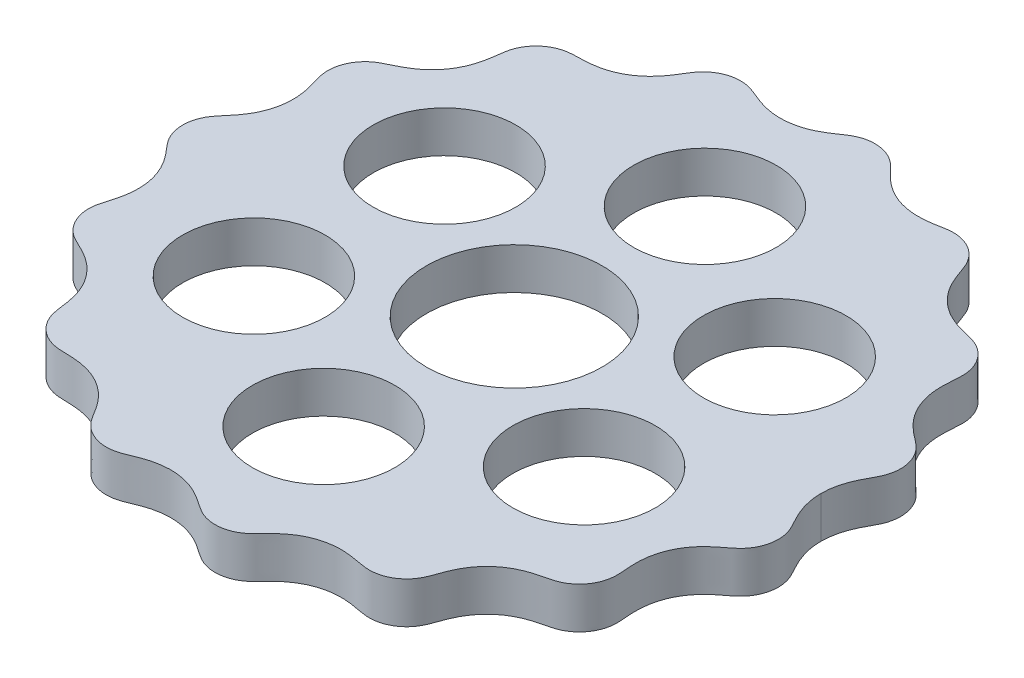
SolidWorks part; units mm, degrees
ref_plane "Front Plane" through (0, 0, 0) normal (0, 0, 1) x (1, 0, 0)
ref_plane "Top Plane" through (0, 0, 0) normal (0, 1, 0) x (1, 0, 0)
ref_plane "Right Plane" through (0, 0, 0) normal (1, 0, 0) x (0, 0, -1)
sketch "Sketch1" plane through (0, 0, 0) normal (0, 1, 0) x (1, 0, 0)
  circle A0 centre (0, 0) radius 10.6
  circle A1 centre (0, 0) radius 23 construction
  circle A2 centre (0, 23) radius 8.6
  circle A3 centre (19.9186, 11.5) radius 8.6
  circle A4 centre (19.9186, -11.5) radius 8.6
  circle A5 centre (0, -23) radius 8.6
  circle A6 centre (-19.9186, -11.5) radius 8.6
  circle A7 centre (-19.9186, 11.5) radius 8.6
  spline S0 degree 4 poles (38.6756, 9.5405) (38.7869, 9.3354) (38.9807, 8.9098) (39.18, 8.2438) (39.2638, 7.3275) (39.17, 6.4698) (38.9321, 5.7015) (38.5995, 5.0253) (38.2553, 4.4109) (37.9563, 3.8443) (37.7129, 3.322) (37.522, 2.8468) (37.3939, 2.4766) (37.2981, 2.1548) (37.2278, 1.884) (37.1776, 1.6659) (37.1334, 1.4465) (37.0953, 1.226) (37.0635, 1.0045) (37.0411, 0.8091) (37.0259, 0.6435) (37.0159, 0.5055) (37.0095, 0.392) (37.0035, 0.2438) (36.9999, 0.079) (36.9994, -0.0361) (37.0025, -0.21) (37.0079, -0.366) (37.0181, -0.5474) (37.0358, -0.7626) (37.0623, -1.0007) (37.0996, -1.2541) (37.1417, -1.4901) (37.1867, -1.7077) (37.276, -2.0862) (37.4326, -2.6197) (37.6503, -3.1917) (37.9334, -3.7956) (38.206, -4.3157) (38.4505, -4.7606) (38.7069, -5.2352) (38.9418, -5.7567) (39.1379, -6.3788) (39.248, -7.1039) (39.2286, -7.94) (39.0193, -8.8558) (38.5776, -9.8235) (37.821, -10.7544) (36.8481, -11.435) (35.9255, -12.1707) (35.1552, -12.9314) (34.5438, -13.6951) (33.8952, -14.742) (33.4284, -15.8904) (33.1613, -17.1041) (33.0908, -18.2767) (33.1179, -19.1348) (33.1846, -19.9227) (33.2426, -20.6446) (33.2196, -21.4379) (33.0363, -22.2817) (32.6622, -23.1285) (32.0787, -23.9264) (31.2705, -24.6475) (30.2129, -25.1958) (29.0562, -25.4259) (27.9212, -25.7148) (26.9129, -26.088) (26.0467, -26.5265) (25.2315, -27.0702) (24.4863, -27.7162) (23.8232, -28.4568) (23.2548, -29.2804) (22.819, -30.1054) (22.4892, -30.9045) (22.2262, -31.656) (21.9863, -32.3444) (21.6457, -33.0672) (21.1369, -33.7721) (20.4446, -34.4052) (19.5735, -34.9081) (18.6791, -35.1912) (17.8142, -35.2793) (17.018, -35.2129) (16.3018, -35.0765) (15.5195, -34.9284) (14.6625, -34.8147) (13.4804, -34.7697) (12.2411, -34.9196) (11.052, -35.2755) (9.9494, -35.8202) (9.1364, -36.3513) (8.3091, -37.0378) (7.4914, -37.8764) (6.7137, -38.763) (5.7101, -39.4048) (4.6815, -39.7442) (3.6987, -39.8506) (2.7784, -39.7512) (1.9559, -39.488) (1.2575, -39.1113) (0.6613, -38.7001) (0.0122, -38.2484) (-0.7173, -37.7958) (-1.768, -37.2706) (-2.9527, -36.8951) (-4.1807, -36.7251) (-5.4116, -36.7634) (-6.3787, -36.9109) (-7.4226, -37.1978) (-8.5211, -37.6287) (-9.5969, -38.1313) (-10.7814, -38.3206) (-11.8653, -38.2177) (-12.81, -37.9179) (-13.7654, -37.3701) (-14.6397, -36.51) (-15.225, -35.4471) (-15.8752, -34.4321) (-16.7227, -33.382) (-17.6452, -32.5494) (-18.6953, -31.8812) (-19.8393, -31.4031) (-20.7931, -31.1347) (-21.8817, -30.9645) (-23.0854, -30.9087) (-24.2988, -30.9334) (-25.4807, -30.6062) (-26.4329, -30.0527) (-27.1648, -29.3844) (-27.7959, -28.4973) (-28.2242, -27.3768) (-28.3269, -26.1938) (-28.503, -25.027) (-28.7764, -23.9796) (-29.1322, -23.0683) (-29.7145, -21.9831) (-30.4757, -21.0047) (-31.3933, -20.1664) (-32.3735, -19.5191) (-33.1302, -19.1136) (-33.8459, -18.7774) (-34.5001, -18.4667) (-35.1756, -18.0501) (-35.8147, -17.4694) (-36.361, -16.7221) (-36.7603, -15.8178) (-36.9806, -14.7573) (-36.9266, -13.5673) (-36.5476, -12.4504) (-36.2302, -11.323) (-36.0493, -10.2632) (-35.996, -9.2938) (-36.0592, -8.316) (-36.2461, -7.3476) (-36.5559, -6.4031) (-36.985, -5.499) (-37.4816, -4.7092) (-38.0086, -4.024) (-38.5281, -3.4205) (-39.0041, -2.8683) (-39.353, -2.3666) (-39.5782, -1.9309) (-39.7176, -1.5888) (-39.7983, -1.3525) (-39.8659, -1.1123) (-39.9132, -0.899) (-39.9453, -0.714) (-39.9664, -0.5608) (-39.98, -0.4381) (-39.9901, -0.3108) (-39.9969, -0.1759) (-40.0009, -0.0264) (-39.9998, 0.101) (-39.9919, 0.3019) (-39.9779, 0.461) (-39.962, 0.5936) (-39.9468, 0.7) (-39.9245, 0.8336) (-39.8928, 0.9931) (-39.8356, 1.2296) (-39.7321, 1.5628) (-39.5698, 1.9581) (-39.3263, 2.4015) (-39.0212, 2.8342) (-38.6301, 3.3062) (-38.1713, 3.8306) (-37.748, 4.3543) (-37.3751, 4.8861) (-37.0367, 5.4401) (-36.6355, 6.2077) (-36.2169, 7.3272) (-36.0304, 8.4018) (-36.0089, 9.2689) (-36.0283, 9.7011) knots 0 0 0 0 0 0.006139 0.012278 0.018165 0.024053 0.028687 0.033322 0.037957 0.042591 0.045535 0.048479 0.051424 0.052896 0.054368 0.05584 0.057312 0.058784 0.060256 0.061728 0.062464 0.0632 0.063936 0.064672 0.066144 0.067103 0.068061 0.06902 0.069978 0.071895 0.073812 0.075274 0.076735 0.078197 0.079659 0.085505 0.091352 0.094275 0.097198 0.100954 0.104711 0.108467 0.112223 0.11807 0.123916 0.130339 0.136761 0.145879 0.154997 0.161421 0.167846 0.17427 0.180694 0.193737 0.200258 0.206779 0.211542 0.216304 0.221067 0.225829 0.232349 0.238869 0.245245 0.251622 0.260677 0.269731 0.27611 0.282488 0.288866 0.295244 0.301811 0.308378 0.314945 0.321512 0.326307 0.331102 0.335897 0.340691 0.347256 0.353821 0.360386 0.366951 0.371745 0.37654 0.381335 0.38613 0.392697 0.399264 0.412398 0.418776 0.425154 0.431532 0.437911 0.446965 0.45602 0.462396 0.468773 0.475293 0.481813 0.486575 0.491338 0.4961 0.500863 0.507384 0.513905 0.526948 0.533372 0.539796 0.54622 0.552645 0.561763 0.570881 0.577303 0.583726 0.59023 0.596734 0.606103 0.615471 0.621978 0.628484 0.641498 0.648004 0.654511 0.661018 0.667524 0.676893 0.686261 0.692765 0.699269 0.705692 0.712114 0.721232 0.730351 0.736775 0.743199 0.749623 0.756047 0.76909 0.775611 0.782133 0.786895 0.791658 0.79642 0.801182 0.807702 0.814222 0.820599 0.826976 0.83603 0.845085 0.851463 0.857841 0.864219 0.870597 0.877164 0.883732 0.890299 0.896866 0.90166 0.906455 0.91125 0.916045 0.917686 0.919327 0.920968 0.922609 0.924251 0.925071 0.925892 0.926712 0.927533 0.928354 0.929174 0.930597 0.93202 0.932732 0.933444 0.934155 0.934867 0.93629 0.937713 0.940559 0.944036 0.947513 0.950991 0.954468 0.960159 0.965851 0.968697 0.971542 0.977234 0.988617 1 1 1 1 1 construction
  spline S1 degree 4 poles (37, 0) (37, -0.0314) (37.0005, -0.095) (37.0025, -0.21) (37.0079, -0.366) (37.0181, -0.5474) (37.0358, -0.7626) (37.0623, -1.0007) (37.0996, -1.2541) (37.1417, -1.4901) (37.1867, -1.7077) (37.276, -2.0862) (37.4326, -2.6197) (37.6503, -3.1917) (37.9334, -3.7956) (38.206, -4.3157) (38.4505, -4.7606) (38.7069, -5.2352) (38.9418, -5.7567) (39.1379, -6.3788) (39.248, -7.1039) (39.2286, -7.94) (39.0193, -8.8558) (38.5776, -9.8235) (37.821, -10.7544) (36.8481, -11.435) (35.9255, -12.1707) (35.1552, -12.9314) (34.5438, -13.6951) (33.8952, -14.742) (33.4284, -15.8904) (33.1613, -17.1041) (33.0908, -18.2767) (33.1179, -19.1348) (33.1846, -19.9227) (33.2426, -20.6446) (33.2196, -21.4379) (33.0363, -22.2817) (32.6622, -23.1285) (32.0787, -23.9264) (31.2705, -24.6475) (30.2129, -25.1958) (29.0562, -25.4259) (27.9212, -25.7148) (26.9129, -26.088) (26.0467, -26.5265) (25.2315, -27.0702) (24.4863, -27.7162) (23.8232, -28.4568) (23.2548, -29.2804) (22.819, -30.1054) (22.4892, -30.9045) (22.2262, -31.656) (21.9863, -32.3444) (21.6457, -33.0672) (21.1369, -33.7721) (20.4446, -34.4052) (19.5735, -34.9081) (18.6791, -35.1912) (17.8142, -35.2793) (17.018, -35.2129) (16.3018, -35.0765) (15.5195, -34.9284) (14.6625, -34.8147) (13.4804, -34.7697) (12.2411, -34.9196) (11.052, -35.2755) (9.9494, -35.8202) (9.1364, -36.3513) (8.3091, -37.0378) (7.4914, -37.8764) (6.7137, -38.763) (5.7101, -39.4048) (4.6815, -39.7442) (3.6987, -39.8506) (2.7784, -39.7512) (1.9559, -39.488) (1.2575, -39.1113) (0.6613, -38.7001) (0.0122, -38.2484) (-0.7173, -37.7958) (-1.768, -37.2706) (-2.9527, -36.8951) (-4.1807, -36.7251) (-5.4116, -36.7634) (-6.3787, -36.9109) (-7.4226, -37.1978) (-8.5211, -37.6287) (-9.5969, -38.1313) (-10.7814, -38.3206) (-11.8653, -38.2177) (-12.81, -37.9179) (-13.7654, -37.3701) (-14.6397, -36.51) (-15.225, -35.4471) (-15.8752, -34.4321) (-16.7227, -33.382) (-17.6452, -32.5494) (-18.6953, -31.8812) (-19.8393, -31.4031) (-20.7931, -31.1347) (-21.8817, -30.9645) (-23.0854, -30.9087) (-24.2988, -30.9334) (-25.4807, -30.6062) (-26.4329, -30.0527) (-27.1648, -29.3844) (-27.7959, -28.4973) (-28.2242, -27.3768) (-28.3269, -26.1938) (-28.503, -25.027) (-28.7764, -23.9796) (-29.1322, -23.0683) (-29.7145, -21.9831) (-30.4757, -21.0047) (-31.3933, -20.1664) (-32.3735, -19.5191) (-33.1302, -19.1136) (-33.8459, -18.7774) (-34.5001, -18.4667) (-35.1756, -18.0501) (-35.8147, -17.4694) (-36.361, -16.7221) (-36.7603, -15.8178) (-36.9806, -14.7573) (-36.9266, -13.5673) (-36.5476, -12.4504) (-36.2302, -11.323) (-36.0493, -10.2632) (-35.996, -9.2938) (-36.0592, -8.316) (-36.2461, -7.3476) (-36.5559, -6.4031) (-36.985, -5.499) (-37.4816, -4.7092) (-38.0086, -4.024) (-38.5281, -3.4205) (-39.0041, -2.8683) (-39.353, -2.3666) (-39.5782, -1.9309) (-39.7176, -1.5888) (-39.7983, -1.3525) (-39.8659, -1.1123) (-39.9132, -0.899) (-39.9453, -0.714) (-39.9664, -0.5608) (-39.98, -0.4381) (-39.9901, -0.3108) (-39.9969, -0.1759) (-39.9994, -0.0812) (-40, -0.0269) (-40, 0) knots 0.066144 0.066144 0.066144 0.066144 0.066144 0.067103 0.068061 0.06902 0.069978 0.071895 0.073812 0.075274 0.076735 0.078197 0.079659 0.085505 0.091352 0.094275 0.097198 0.100954 0.104711 0.108467 0.112223 0.11807 0.123916 0.130339 0.136761 0.145879 0.154997 0.161421 0.167846 0.17427 0.180694 0.193737 0.200258 0.206779 0.211542 0.216304 0.221067 0.225829 0.232349 0.238869 0.245245 0.251622 0.260677 0.269731 0.27611 0.282488 0.288866 0.295244 0.301811 0.308378 0.314945 0.321512 0.326307 0.331102 0.335897 0.340691 0.347256 0.353821 0.360386 0.366951 0.371745 0.37654 0.381335 0.38613 0.392697 0.399264 0.412398 0.418776 0.425154 0.431532 0.437911 0.446965 0.45602 0.462396 0.468773 0.475293 0.481813 0.486575 0.491338 0.4961 0.500863 0.507384 0.513905 0.526948 0.533372 0.539796 0.54622 0.552645 0.561763 0.570881 0.577303 0.583726 0.59023 0.596734 0.606103 0.615471 0.621978 0.628484 0.641498 0.648004 0.654511 0.661018 0.667524 0.676893 0.686261 0.692765 0.699269 0.705692 0.712114 0.721232 0.730351 0.736775 0.743199 0.749623 0.756047 0.76909 0.775611 0.782133 0.786895 0.791658 0.79642 0.801182 0.807702 0.814222 0.820599 0.826976 0.83603 0.845085 0.851463 0.857841 0.864219 0.870597 0.877164 0.883732 0.890299 0.896866 0.90166 0.906455 0.91125 0.916045 0.917686 0.919327 0.920968 0.922609 0.924251 0.925071 0.925892 0.926712 0.927533 0.928354 0.929174 0.929174 0.929174 0.929174 0.929174
  spline S2 degree 4 poles (-36.0283, -9.7011) (-36.0089, -9.2689) (-36.025, -8.6185) (-36.1423, -7.7571) (-36.4452, -6.7165) (-36.7773, -5.9157) (-37.1923, -5.1548) (-37.6189, -4.528) (-38.0202, -4.0177) (-38.3849, -3.5864) (-38.6992, -3.2229) (-38.979, -2.8851) (-39.2119, -2.5638) (-39.3869, -2.2834) (-39.514, -2.0514) (-39.6452, -1.7744) (-39.7518, -1.4995) (-39.8356, -1.2297) (-39.8991, -0.9667) (-39.9398, -0.7534) (-39.9703, -0.5412) (-39.9907, -0.329) (-39.9998, -0.1024) (-40.0009, 0.0274) (-39.9969, 0.174) (-39.9901, 0.3085) (-39.98, 0.4378) (-39.9664, 0.5616) (-39.9495, 0.6838) (-39.9292, 0.8064) (-39.9056, 0.9291) (-39.8785, 1.0511) (-39.8405, 1.2024) (-39.7882, 1.382) (-39.7175, 1.5887) (-39.6127, 1.8466) (-39.4787, 2.1231) (-39.3107, 2.4141) (-39.1049, 2.7153) (-38.8813, 3.0032) (-38.6471, 3.2825) (-38.3498, 3.6277) (-37.9529, 4.0962) (-37.4817, 4.7093) (-36.9849, 5.4989) (-36.556, 6.4033) (-36.1702, 7.5783) (-35.9868, 8.7988) (-36.0091, 10.0244) (-36.2006, 11.152) (-36.4085, 11.955) (-36.6307, 12.6803) (-36.8216, 13.3417) (-36.9923, 14.3318) (-36.9049, 15.4222) (-36.5044, 16.5243) (-35.815, 17.4697) (-35.1754, 18.05) (-34.5001, 18.4666) (-33.846, 18.7777) (-32.9056, 19.2181) (-31.7252, 19.8872) (-30.4396, 20.9666) (-29.2852, 22.5861) (-28.6866, 24.1372) (-28.4341, 25.439) (-28.3116, 26.4395) (-28.2186, 27.1266) (-28.0361, 27.8709) (-27.6947, 28.6385) (-27.1647, 29.385) (-26.4334, 30.0526) (-25.6346, 30.5161) (-24.8231, 30.7888) (-24.0469, 30.8992) (-23.3347, 30.9203) (-22.3064, 30.9378) (-20.9635, 31.0586) (-19.3449, 31.507) (-17.6134, 32.5067) (-16.4158, 33.6842) (-15.6397, 34.7868) (-15.1104, 35.6686) (-14.7361, 36.2748) (-14.2524, 36.8918) (-13.6104, 37.4583) (-12.8096, 37.9183) (-11.8658, 38.2178) (-10.9543, 38.3035) (-10.1188, 38.2154) (-9.383, 38.0014) (-8.7414, 37.7383) (-7.8138, 37.3442) (-6.5601, 36.912) (-4.9175, 36.6548) (-2.9379, 36.8448) (-1.3603, 37.4184) (-0.1906, 38.1061) (0.661, 38.7003) (1.2575, 39.1113) (1.9559, 39.4878) (2.7783, 39.7515) (3.9418, 39.8759) (5.0965, 39.6717) (6.0845, 39.2022) (6.8565, 38.5593) (7.3339, 38.0633) (7.8509, 37.5082) (8.4424, 36.9267) (9.3231, 36.1969) (10.5884, 35.4356) (11.9992, 34.9487) (13.4803, 34.7698) (14.6625, 34.8147) (15.5194, 34.9284) (16.3018, 35.0765) (17.0179, 35.2129) (17.8142, 35.2793) (18.6791, 35.1911) (19.5735, 34.9082) (20.4445, 34.4052) (21.137, 33.7722) (21.5918, 33.1415) (21.8696, 32.5926) (22.0759, 32.0862) (22.2266, 31.6561) (22.3766, 31.2261) (22.5937, 30.6514) (22.8615, 30.0249) (23.2551, 29.2802) (23.8228, 28.4571) (24.6491, 27.5346) (25.8025, 26.6152) (27.2181, 25.9053) (28.8176, 25.4727) (30.4528, 25.1488) (31.6988, 24.3833) (32.5609, 23.3518) (33.0376, 22.2818) (33.2189, 21.4379) (33.243, 20.6446) (33.1848, 19.9227) (33.0963, 18.888) (33.0853, 17.5312) (33.3775, 15.8781) (34.2027, 14.0687) (35.2468, 12.7747) (36.2479, 11.9052) (37.0531, 11.2989) (37.6016, 10.8748) (38.155, 10.3445) (38.649, 9.665) (39.0305, 8.8328) (39.243, 7.8658) (39.2451, 6.9422) (39.0753, 6.1031) (38.7832, 5.3754) (38.4446, 4.7486) (38.1266, 4.173) (37.8549, 3.634) (37.633, 3.1317) (37.4786, 2.7272) (37.3626, 2.3747) (37.2774, 2.0775) (37.2164, 1.8379) (37.1626, 1.5964) (37.1163, 1.3536) (37.0774, 1.1094) (37.0502, 0.8937) (37.0316, 0.7109) (37.0194, 0.5584) (37.0116, 0.4331) (37.0042, 0.2696) (36.9994, 0.0658) (36.9993, -0.087) (37.0071, -0.3742) (37.0226, -0.616) (37.0458, -0.8587) (37.0767, -1.1038) (37.1247, -1.4076) (37.1852, -1.7092) (37.2578, -2.0082) (37.3591, -2.3632) (37.4739, -2.7141) (37.627, -3.1167) (37.8469, -3.6171) (38.1165, -4.154) (38.4326, -4.7273) (38.7709, -5.3508) (39.0661, -6.0733) (39.2414, -6.9072) (39.2472, -7.9128) (39.0566, -8.7198) (38.8323, -9.2517) (38.6756, -9.5405) knots 0 0 0 0 0 0.011383 0.017074 0.022766 0.028458 0.034149 0.039841 0.042687 0.045532 0.049009 0.052487 0.054225 0.055964 0.057702 0.059441 0.062287 0.06371 0.065133 0.066556 0.06798 0.069403 0.070826 0.071646 0.072467 0.073288 0.074108 0.074929 0.075749 0.07657 0.077391 0.078211 0.079032 0.080673 0.082314 0.083955 0.086353 0.08875 0.091148 0.093545 0.095942 0.09834 0.103134 0.109701 0.116269 0.122836 0.129403 0.142159 0.148537 0.154915 0.159443 0.16397 0.168497 0.173024 0.185778 0.192298 0.198818 0.20358 0.208342 0.213105 0.217867 0.23091 0.243953 0.256801 0.269649 0.274209 0.278768 0.283327 0.287886 0.294308 0.300731 0.307235 0.313739 0.318423 0.323107 0.327792 0.332476 0.345489 0.358502 0.371516 0.384529 0.389213 0.393897 0.398582 0.403266 0.40977 0.416274 0.422697 0.429119 0.433678 0.438237 0.442796 0.447355 0.460204 0.473052 0.486095 0.499137 0.5039 0.508662 0.513425 0.518187 0.524707 0.531227 0.54398 0.548508 0.553035 0.557562 0.56209 0.568468 0.574846 0.587602 0.600736 0.607303 0.613871 0.618665 0.62346 0.628255 0.633049 0.639614 0.646179 0.652744 0.659309 0.664104 0.666501 0.668898 0.673693 0.67609 0.678488 0.685055 0.691622 0.698189 0.704756 0.717512 0.730269 0.739323 0.748378 0.761131 0.767651 0.774171 0.778933 0.783696 0.788458 0.793221 0.806263 0.819306 0.832154 0.845003 0.849562 0.854121 0.85868 0.863239 0.869662 0.876084 0.882588 0.889092 0.893777 0.898461 0.903145 0.907829 0.911083 0.914336 0.917589 0.919216 0.920842 0.922469 0.924096 0.925722 0.927349 0.928976 0.929789 0.930602 0.931416 0.932229 0.933856 0.935474 0.937093 0.938711 0.94033 0.941948 0.943567 0.946804 0.948422 0.950041 0.953278 0.956515 0.959752 0.964416 0.96908 0.973744 0.978408 0.984882 0.991355 1 1 1 1 1 construction
  spline S3 degree 4 poles (-40, 0) (-40, 0.0269) (-39.9994, 0.0811) (-39.9969, 0.174) (-39.9901, 0.3085) (-39.98, 0.4378) (-39.9664, 0.5616) (-39.9495, 0.6838) (-39.9292, 0.8064) (-39.9056, 0.9291) (-39.8785, 1.0511) (-39.8405, 1.2024) (-39.7882, 1.382) (-39.7175, 1.5887) (-39.6127, 1.8466) (-39.4787, 2.1231) (-39.3107, 2.4141) (-39.1049, 2.7153) (-38.8813, 3.0032) (-38.6471, 3.2825) (-38.3498, 3.6277) (-37.9529, 4.0962) (-37.4817, 4.7093) (-36.9849, 5.4989) (-36.556, 6.4033) (-36.1702, 7.5783) (-35.9868, 8.7988) (-36.0091, 10.0244) (-36.2006, 11.152) (-36.4085, 11.955) (-36.6307, 12.6803) (-36.8216, 13.3417) (-36.9923, 14.3318) (-36.9049, 15.4222) (-36.5044, 16.5243) (-35.815, 17.4697) (-35.1754, 18.05) (-34.5001, 18.4666) (-33.846, 18.7777) (-32.9056, 19.2181) (-31.7252, 19.8872) (-30.4396, 20.9666) (-29.2852, 22.5861) (-28.6866, 24.1372) (-28.4341, 25.439) (-28.3116, 26.4395) (-28.2186, 27.1266) (-28.0361, 27.8709) (-27.6947, 28.6385) (-27.1647, 29.385) (-26.4334, 30.0526) (-25.6346, 30.5161) (-24.8231, 30.7888) (-24.0469, 30.8992) (-23.3347, 30.9203) (-22.3064, 30.9378) (-20.9635, 31.0586) (-19.3449, 31.507) (-17.6134, 32.5067) (-16.4158, 33.6842) (-15.6397, 34.7868) (-15.1104, 35.6686) (-14.7361, 36.2748) (-14.2524, 36.8918) (-13.6104, 37.4583) (-12.8096, 37.9183) (-11.8658, 38.2178) (-10.9543, 38.3035) (-10.1188, 38.2154) (-9.383, 38.0014) (-8.7414, 37.7383) (-7.8138, 37.3442) (-6.5601, 36.912) (-4.9175, 36.6548) (-2.9379, 36.8448) (-1.3603, 37.4184) (-0.1906, 38.1061) (0.661, 38.7003) (1.2575, 39.1113) (1.9559, 39.4878) (2.7783, 39.7515) (3.9418, 39.8759) (5.0965, 39.6717) (6.0845, 39.2022) (6.8565, 38.5593) (7.3339, 38.0633) (7.8509, 37.5082) (8.4424, 36.9267) (9.3231, 36.1969) (10.5884, 35.4356) (11.9992, 34.9487) (13.4803, 34.7698) (14.6625, 34.8147) (15.5194, 34.9284) (16.3018, 35.0765) (17.0179, 35.2129) (17.8142, 35.2793) (18.6791, 35.1911) (19.5735, 34.9082) (20.4445, 34.4052) (21.137, 33.7722) (21.5918, 33.1415) (21.8696, 32.5926) (22.0759, 32.0862) (22.2266, 31.6561) (22.3766, 31.2261) (22.5937, 30.6514) (22.8615, 30.0249) (23.2551, 29.2802) (23.8228, 28.4571) (24.6491, 27.5346) (25.8025, 26.6152) (27.2181, 25.9053) (28.8176, 25.4727) (30.4528, 25.1488) (31.6988, 24.3833) (32.5609, 23.3518) (33.0376, 22.2818) (33.2189, 21.4379) (33.243, 20.6446) (33.1848, 19.9227) (33.0963, 18.888) (33.0853, 17.5312) (33.3775, 15.8781) (34.2027, 14.0687) (35.2468, 12.7747) (36.2479, 11.9052) (37.0531, 11.2989) (37.6016, 10.8748) (38.155, 10.3445) (38.649, 9.665) (39.0305, 8.8328) (39.243, 7.8658) (39.2451, 6.9422) (39.0753, 6.1031) (38.7832, 5.3754) (38.4446, 4.7486) (38.1266, 4.173) (37.8549, 3.634) (37.633, 3.1317) (37.4786, 2.7272) (37.3626, 2.3747) (37.2774, 2.0775) (37.2164, 1.8379) (37.1626, 1.5964) (37.1163, 1.3536) (37.0774, 1.1094) (37.0502, 0.8937) (37.0316, 0.7109) (37.0194, 0.5584) (37.0116, 0.4331) (37.0042, 0.2696) (37.001, 0.1335) (37, 0.0534) (37, 0) knots 0.070826 0.070826 0.070826 0.070826 0.070826 0.071646 0.072467 0.073288 0.074108 0.074929 0.075749 0.07657 0.077391 0.078211 0.079032 0.080673 0.082314 0.083955 0.086353 0.08875 0.091148 0.093545 0.095942 0.09834 0.103134 0.109701 0.116269 0.122836 0.129403 0.142159 0.148537 0.154915 0.159443 0.16397 0.168497 0.173024 0.185778 0.192298 0.198818 0.20358 0.208342 0.213105 0.217867 0.23091 0.243953 0.256801 0.269649 0.274209 0.278768 0.283327 0.287886 0.294308 0.300731 0.307235 0.313739 0.318423 0.323107 0.327792 0.332476 0.345489 0.358502 0.371516 0.384529 0.389213 0.393897 0.398582 0.403266 0.40977 0.416274 0.422697 0.429119 0.433678 0.438237 0.442796 0.447355 0.460204 0.473052 0.486095 0.499137 0.5039 0.508662 0.513425 0.518187 0.524707 0.531227 0.54398 0.548508 0.553035 0.557562 0.56209 0.568468 0.574846 0.587602 0.600736 0.607303 0.613871 0.618665 0.62346 0.628255 0.633049 0.639614 0.646179 0.652744 0.659309 0.664104 0.666501 0.668898 0.673693 0.67609 0.678488 0.685055 0.691622 0.698189 0.704756 0.717512 0.730269 0.739323 0.748378 0.761131 0.767651 0.774171 0.778933 0.783696 0.788458 0.793221 0.806263 0.819306 0.832154 0.845003 0.849562 0.854121 0.85868 0.863239 0.869662 0.876084 0.882588 0.889092 0.893777 0.898461 0.903145 0.907829 0.911083 0.914336 0.917589 0.919216 0.920842 0.922469 0.924096 0.925722 0.927349 0.928976 0.929789 0.930602 0.931416 0.932229 0.933856 0.933856 0.933856 0.933856 0.933856
  point P24 (0, 0)
  dimension "D1" = 21.2
  dimension "D2" = 17.2
  dimension "D4" = 46
  dimension "D3" = 6
extrude "Boss-Extrude1" add sketch "Sketch1" along normal blind 5
